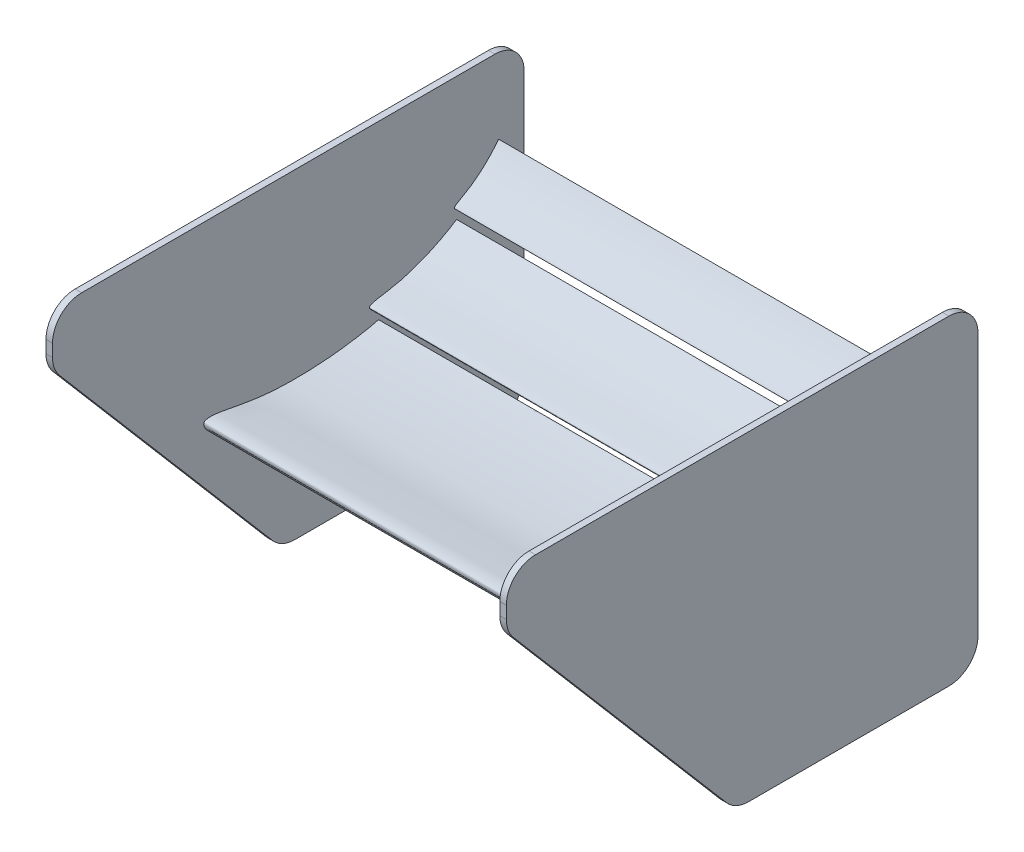
SolidWorks part; units mm, degrees
ref_plane "Front Plane" through (0, 0, 0) normal (0, 0, 1) x (1, 0, 0)
ref_plane "Top Plane" through (0, 0, 0) normal (0, 1, 0) x (1, 0, 0)
ref_plane "Right Plane" through (0, 0, 0) normal (1, 0, 0) x (0, 0, -1)
ref_plane "Soft Top Limit" through (0, 1174.6, 0) normal (0, 1, 0) x (1, 0, 0)
ref_plane "Soft Rear Limit" through (0, 0, -1192.975) normal (0, 0, 1) x (1, 0, 0)
ref_plane "Soft Right Limit" through (-501.65, 0, 0) normal (1, 0, 0) x (0, 0, -1)
ref_plane "Soft Left Limit" through (501.65, 0, 0) normal (1, 0, 0) x (0, 0, -1)
ref_plane "Soft Front Limit" through (0, 0, -165.1) normal (0, 0, 1) x (1, 0, 0)
ref_plane "Slant Limit" through (0, 528.6251, -619.2711) normal (0, -0.6492, 0.7606) x (1, 0, 0)
ref_plane "Bottom" through (0, 476.25, 0) normal (0, 1, 0) x (1, 0, 0)
ref_plane "Midplane" through (0, 0, 0) normal (1, 0, 0) x (0, 0, -1)
curve "Curve2"
  spline degree 3 poles (0, 2520.0207, 6.126) (0, 2544.889, -1.81) (0, 2521.8965, 7.8839) (0, 2505.3253, 17.7145) (0, 2467.7144, 38.5723) (0, 2424.2142, 62.3813) (0, 2368.0949, 87.8078) (0, 2301.3729, 113.3478) (0, 2223.8362, 140.5377) (0, 2136.6129, 169.2441) (0, 2040.932, 199.097) (0, 1938.2341, 229.6055) (0, 1829.9414, 260.0781) (0, 1717.5266, 289.8586) (0, 1602.4273, 318.1375) (0, 1486.0259, 343.9752) (0, 1369.6902, 366.5754) (0, 1254.3666, 384.7865) (0, 1140.5393, 397.0034) (0, 1028.6357, 403.0127) (0, 919.0585, 402.9406) (0, 812.3986, 397.0375) (0, 709.2785, 385.5985) (0, 610.4299, 369.039) (0, 516.5862, 348.1086) (0, 428.5874, 323.3415) (0, 347.2653, 295.2055) (0, 273.332, 264.2656) (0, 207.4209, 231.0894) (0, 150.0337, 196.3024) (0, 101.596, 160.572) (0, 62.3674, 124.65) (0, 32.4977, 89.3959) (0, 12.0597, 55.6746) (0, 1.683, 26.6201) (0, -0.5567, 6.5526) (0, 0.5894, -3.9947) (0, 1.6947, -9.1451) (0, 2.8711, -12.4915) (0, 3.9449, -14.9776) (0, 4.8993, -16.669) (0, 5.9763, -18.2433) (0, 7.3264, -19.6365) (0, 8.8595, -20.9434) (0, 11.1868, -22.7306) (0, 14.6073, -24.7406) (0, 20.085, -27.4067) (0, 26.8353, -29.9257) (0, 44.6446, -35.1819) (0, 77.8093, -38.8998) (0, 130.2841, -38.2927) (0, 196.3018, -31.4611) (0, 276.2192, -18.4434) (0, 370.8288, 0.8611) (0, 480.7331, 24.811) (0, 605.9792, 50.0099) (0, 745.0759, 74.1542) (0, 895.4497, 95.0846) (0, 1053.6786, 110.004) (0, 1215.6439, 118.3392) (0, 1377.6893, 121.6348) (0, 1537.1174, 120.5125) (0, 1691.5141, 115.2051) (0, 1838.3121, 105.7388) (0, 1975.028, 93.0069) (0, 2099.5942, 78.4581) (0, 2210.5746, 63.1262) (0, 2306.3634, 48.0168) (0, 2387.2069, 33.7158) (0, 2449.0745, 22.0129) (0, 2499.1865, 10.4993) (0, 2520.0207, 6.126) (0, 2544.889, -1.81) (0, 2521.8965, 7.8839) knots -0.016237 -0.007308 -0.001841 0 0.001813 0.006911 0.014576 0.024172 0.035572 0.049013 0.064513 0.081849 0.100772 0.120997 0.142228 0.164173 0.186537 0.209023 0.231367 0.25332 0.274804 0.295858 0.316449 0.336531 0.356033 0.374893 0.39299 0.410197 0.426388 0.441459 0.455334 0.467938 0.479236 0.489204 0.497851 0.505194 0.511308 0.515097 0.516441 0.517273 0.51806 0.518436 0.518797 0.519154 0.519508 0.519887 0.520289 0.52116 0.522116 0.52372 0.525214 0.532575 0.542381 0.554776 0.569931 0.588005 0.609188 0.633329 0.660001 0.688743 0.718873 0.749543 0.780127 0.810209 0.839387 0.867183 0.893104 0.91676 0.937874 0.956199 0.971544 0.983763 0.992692 0.998159 1 1.001813 1.006911 1.014576 periodic
sketch "Sketch4" plane through (0, 0, 0) normal (1, 0, 0) x (0, 0, -1)
  line L0 (165.1, 1174.6) -> (165.1, 1060.6753) construction
  line L1 (165.1, 1060.6753) -> (663.9798, 476.25) construction
  line L2 (663.9798, 476.25) -> (1192.975, 476.25) construction
  line L3 (1192.975, 476.25) -> (1192.975, 1174.6) construction
  line L4 (1192.975, 1174.6) -> (165.1, 1174.6) construction
  line L5 (509.9361, 1174.6) -> (-509.9361, 1174.6) construction
  line L6 (165.1, 67.0076) -> (165.1, -67.0076) construction
  line L7 (364.7288, 826.8151) -> (873.8134, 230.4351) construction
  line L8 (279.3831, 476.25) -> (-279.3831, 476.25) construction
  line L9 (1192.975, 353.2696) -> (1192.975, -353.2696) construction
  line L10 (520.9997, -714.1403) -> (468.3643, 2301.3403) construction
  line L11 (899.2344, -552.3901) -> (852.0136, 2152.8888) construction
  line L12 (875.624, 800.2494) -> (494.682, 793.6) construction
  line L13 (393.082, 793.6) -> (1192.975, 793.6) construction
  line L14 (834.2182, 888.0761) -> (877.4997, 775.3239) construction
  line L15 (1023.7202, 961.4213) -> (1067.4047, 847.6194) construction
  line L16 (1045.5625, 904.5204) -> (855.8589, 831.7) construction
  line L17 (360.5589, 831.7) -> (1192.975, 831.7) construction
  line L18 (1012.8055, 959.673) -> (1069.6968, 894.227) construction
  line L19 (1118.0222, 1032.2151) -> (1156.1764, 988.3238) construction
  line L20 (1137.108, 1010.277) -> (1041.2512, 926.95) construction
  line L21 (279.2512, 926.95) -> (1192.975, 926.95) construction
  spline S0 degree 3 poles (872.6415, 799.2849) (876.3531, 800.532) (872.9268, 799.0256) (870.464, 797.5133) (864.8707, 794.2991) (858.4009, 790.6288) (850.0422, 786.6871) (840.0936, 782.7042) (828.5267, 778.449) (815.5105, 773.9443) (801.2285, 769.2484) (785.8955, 764.438) (769.7234, 759.6203) (752.9314, 754.8969) (735.7334, 750.3927) (718.3345, 746.2515) (700.938, 742.5961) (683.6833, 739.6013) (666.6394, 737.5089) (649.8698, 736.3519) (633.4352, 736.1124) (617.4248, 736.754) (601.9327, 738.234) (587.0695, 740.4918) (572.9469, 743.4165) (559.6922, 746.93) (547.4312, 750.964) (536.272, 755.4355) (526.3108, 760.2607) (517.6243, 765.3469) (510.278, 770.5951) (504.3124, 775.893) (499.752, 781.1122) (496.6096, 786.1231) (494.9869, 790.4569) (494.6052, 793.4616) (494.7529, 795.0461) (494.907, 795.8211) (495.0757, 796.3256) (495.2311, 796.701) (495.3704, 796.9568) (495.5283, 797.1954) (495.7276, 797.4074) (495.9546, 797.6069) (496.2995, 797.8803) (496.808, 798.1896) (497.6234, 798.602) (498.6301, 798.9952) (501.2891, 799.8242) (506.2547, 800.4576) (514.1263, 800.4865) (524.0432, 799.6127) (536.059, 797.8429) (550.2927, 795.1638) (566.8309, 791.8229) (585.673, 788.3297) (606.5899, 785.0264) (629.1909, 782.2308) (652.9562, 780.3548) (677.2669, 779.4747) (701.5781, 779.3507) (725.4866, 779.8833) (748.6309, 781.0321) (770.6262, 782.7873) (791.1018, 785.0092) (809.751, 787.4759) (826.3609, 790.029) (840.6928, 792.5139) (852.7851, 794.8435) (862.0372, 796.7401) (869.5268, 798.5814) (872.6415, 799.2849) (876.3531, 800.532) (872.9268, 799.0256) knots -0.016237 -0.007308 -0.001841 0 0.001813 0.006911 0.014576 0.024172 0.035572 0.049013 0.064513 0.081849 0.100772 0.120997 0.142228 0.164173 0.186537 0.209023 0.231367 0.25332 0.274804 0.295858 0.316449 0.336531 0.356033 0.374893 0.39299 0.410197 0.426388 0.441459 0.455334 0.467938 0.479236 0.489204 0.497851 0.505194 0.511308 0.515097 0.516441 0.517273 0.51806 0.518436 0.518797 0.519154 0.519508 0.519887 0.520289 0.52116 0.522116 0.52372 0.525214 0.532575 0.542381 0.554776 0.569931 0.588005 0.609188 0.633329 0.660001 0.688743 0.718873 0.749543 0.780127 0.810209 0.839387 0.867183 0.893104 0.91676 0.937874 0.956199 0.971544 0.983763 0.992692 0.998159 1 1.001813 1.006911 1.014576 only from (875.624, 800.2494) to (875.624, 800.2494)
  spline S1 degree 3 poles (1044.2437, 903.493) (1045.8763, 904.795) (1044.434, 903.415) (1043.4755, 902.2079) (1041.2586, 899.5768) (1038.6857, 896.5572) (1035.2156, 893.057) (1030.9562, 889.2461) (1025.9354, 885.0037) (1020.2338, 880.3718) (1013.9326, 875.4131) (1007.1257, 870.2054) (999.8995, 864.8409) (992.3455, 859.4107) (984.548, 854.0162) (976.5836, 848.767) (968.5318, 843.7617) (960.4305, 839.1134) (952.2703, 834.9557) (944.0769, 831.3169) (935.8841, 828.199) (927.7432, 825.6001) (919.709, 823.5159) (911.8482, 821.9362) (904.2369, 820.8259) (896.9532, 820.169) (890.0725, 819.9542) (883.6642, 820.1596) (877.7917, 820.7608) (872.5106, 821.7253) (867.8715, 823.0155) (863.9153, 824.5825) (860.6777, 826.3663) (858.1889, 828.3044) (856.5851, 830.1804) (855.8457, 831.6166) (855.6307, 832.4377) (855.5665, 832.8542) (855.5591, 833.1378) (855.5685, 833.3543) (855.5916, 833.5079) (855.6272, 833.6563) (855.6884, 833.7989) (855.7658, 833.9403) (855.8888, 834.1402) (856.0872, 834.388) (856.4206, 834.7434) (856.8534, 835.1241) (858.0348, 836.0246) (860.4079, 837.2478) (864.3476, 838.6981) (869.4771, 840.0692) (875.8219, 841.374) (883.4441, 842.6277) (892.3419, 843.9701) (902.4222, 845.6564) (913.5077, 847.8164) (925.3445, 850.538) (937.5972, 853.9328) (949.9415, 857.9263) (962.1481, 862.2987) (974.0332, 866.9268) (985.4229, 871.7244) (996.126, 876.6162) (1005.9825, 881.4647) (1014.879, 886.1027) (1022.7376, 890.4121) (1029.467, 894.2718) (1035.1024, 897.6451) (1039.3933, 900.2833) (1042.811, 902.5722) (1044.2437, 903.493) (1045.8763, 904.795) (1044.434, 903.415) knots -0.016237 -0.007308 -0.001841 0 0.001813 0.006911 0.014576 0.024172 0.035572 0.049013 0.064513 0.081849 0.100772 0.120997 0.142228 0.164173 0.186537 0.209023 0.231367 0.25332 0.274804 0.295858 0.316449 0.336531 0.356033 0.374893 0.39299 0.410197 0.426388 0.441459 0.455334 0.467938 0.479236 0.489204 0.497851 0.505194 0.511308 0.515097 0.516441 0.517273 0.51806 0.518436 0.518797 0.519154 0.519508 0.519887 0.520289 0.52116 0.522116 0.52372 0.525214 0.532575 0.542381 0.554776 0.569931 0.588005 0.609188 0.633329 0.660001 0.688743 0.718873 0.749543 0.780127 0.810209 0.839387 0.867183 0.893104 0.91676 0.937874 0.956199 0.971544 0.983763 0.992692 0.998159 1 1.001813 1.006911 1.014576 only from (1045.5625, 904.5204) to (1045.5625, 904.5204)
  spline S2 degree 3 poles (1136.553, 1009.3917) (1137.2336, 1010.5054) (1136.6814, 1009.3866) (1136.3765, 1008.4726) (1135.6369, 1006.4533) (1134.7712, 1004.1296) (1133.4813, 1001.3319) (1131.7941, 998.183) (1129.7521, 994.6178) (1127.3934, 990.6783) (1124.7524, 986.4187) (1121.8676, 981.9047) (1118.7701, 977.2089) (1115.494, 972.4045) (1112.0673, 967.569) (1108.5115, 962.7832) (1104.8522, 958.122) (1101.0876, 953.6599) (1097.1835, 949.4733) (1093.1489, 945.5844) (1089.0033, 942.0016) (1084.7772, 938.7347) (1080.5038, 935.793) (1076.2244, 933.1846) (1071.9912, 930.9053) (1067.8535, 928.9623) (1063.8579, 927.3652) (1060.05, 926.1159) (1056.4723, 925.2136) (1053.1641, 924.6511) (1050.1635, 924.4171) (1047.5048, 924.4918) (1045.2218, 924.8474) (1043.3456, 925.4536) (1042.0025, 926.2127) (1041.2612, 926.8982) (1040.9594, 927.3345) (1040.8327, 927.5654) (1040.7677, 927.7304) (1040.7269, 927.8596) (1040.7077, 927.9547) (1040.6969, 928.0495) (1040.7023, 928.1464) (1040.7175, 928.2459) (1040.7471, 928.3897) (1040.8106, 928.5776) (1040.9305, 928.8576) (1041.1033, 929.1738) (1041.6047, 929.9553) (1042.737, 931.181) (1044.741, 932.8751) (1047.4608, 934.777) (1050.9085, 936.8999) (1055.1175, 939.2657) (1060.0567, 941.9564) (1065.617, 945.1018) (1071.6664, 948.7404) (1078.0371, 952.8695) (1084.5081, 957.4828) (1090.9049, 962.4674) (1097.1398, 967.6452) (1103.1313, 972.9044) (1108.7955, 978.1572) (1114.0363, 983.3186) (1118.7891, 988.2736) (1123.023, 992.8997) (1126.7176, 997.1108) (1129.8451, 1000.8165) (1132.4339, 1004.0026) (1134.3903, 1006.4695) (1135.9083, 1008.5446) (1136.553, 1009.3917) (1137.2336, 1010.5054) (1136.6814, 1009.3866) knots -0.016237 -0.007308 -0.001841 0 0.001813 0.006911 0.014576 0.024172 0.035572 0.049013 0.064513 0.081849 0.100772 0.120997 0.142228 0.164173 0.186537 0.209023 0.231367 0.25332 0.274804 0.295858 0.316449 0.336531 0.356033 0.374893 0.39299 0.410197 0.426388 0.441459 0.455334 0.467938 0.479236 0.489204 0.497851 0.505194 0.511308 0.515097 0.516441 0.517273 0.51806 0.518436 0.518797 0.519154 0.519508 0.519887 0.520289 0.52116 0.522116 0.52372 0.525214 0.532575 0.542381 0.554776 0.569931 0.588005 0.609188 0.633329 0.660001 0.688743 0.718873 0.749543 0.780127 0.810209 0.839387 0.867183 0.893104 0.91676 0.937874 0.956199 0.971544 0.983763 0.992692 0.998159 1 1.001813 1.006911 1.014576 only from (1137.108, 1010.277) to (1137.108, 1010.277)
  point P36 (0, 0)
  point P44 (1136.348, 1009.194)
  dimension "D1" = 381
  dimension "D2" = 381
  dimension "D3" = 1
  dimension "D4" = 101.6
  dimension "D5" = 203.2
  dimension "D6" = 342.9
  dimension "D7" = 21
  dimension "D8" = 495.3
  dimension "D9" = 127
  dimension "D10" = 247.65
  dimension "D11" = 41
  dimension "D12" = 762
extrude "Boss-Extrude1" add sketch "Sketch4" along normal offset from surface (487.45 mm away) 14.2 up to plane "Soft Left Limit"
sketch "Sketch5" plane through (501.65, 0, 0) normal (1, 0, 0) x (0, 0, -1)
  line L0 (228.6, 1174.6) -> (1129.475, 1174.6)
  line L1 (1192.975, 1111.1) -> (1192.975, 539.75)
  line L2 (1129.475, 476.25) -> (693.2639, 476.25)
  line L3 (644.9672, 498.5228) -> (180.3033, 1042.8649)
  line L4 (165.1, 1084.0921) -> (165.1, 1111.1)
  line L5 (165.1, 67.0076) -> (165.1, -67.0076) construction
  line L6 (509.9361, 1174.6) -> (-509.9361, 1174.6) construction
  line L7 (1192.975, 353.2696) -> (1192.975, -353.2696) construction
  line L8 (279.3831, 476.25) -> (-279.3831, 476.25) construction
  line L9 (364.7288, 826.8151) -> (873.8134, 230.4351) construction
  arc A0 (1129.475, 1174.6) -> (1192.975, 1111.1) centre (1129.475, 1111.1) cw
  arc A1 (1192.975, 539.75) -> (1129.475, 476.25) centre (1129.475, 539.75) cw
  arc A2 (693.2639, 476.25) -> (644.9672, 498.5228) centre (693.2639, 539.75) cw
  arc A3 (180.3033, 1042.8649) -> (165.1, 1084.0921) centre (228.6, 1084.0921) cw
  arc A4 (228.6, 1174.6) -> (165.1, 1111.1) centre (228.6, 1111.1) ccw
  dimension "D1" = 63.5
extrude "Boss-Extrude3" add sketch "Sketch5" against normal up to surface (14.2 mm away)
mirror "Mirror3" about plane through (0, 0, 0) normal (1, 0, 0) of bodies 106
